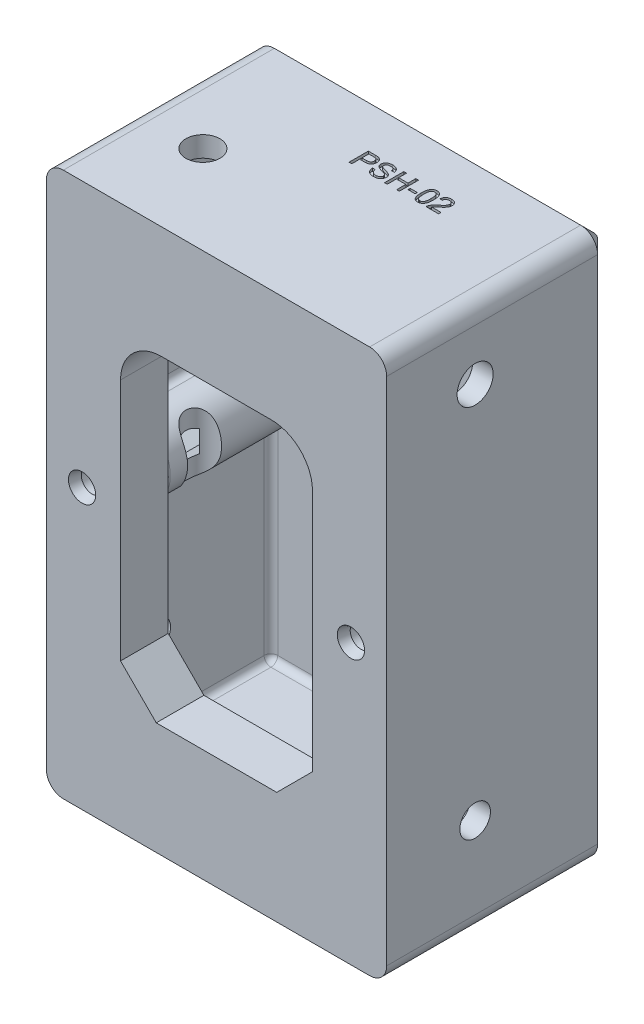
SolidWorks part; units mm, degrees
ref_plane "Front" through (0, 0, 0) normal (0, 0, 1) x (1, 0, 0)
ref_plane "Top" through (0, 0, 0) normal (0, 1, 0) x (1, 0, 0)
ref_plane "Right" through (0, 0, 0) normal (1, 0, 0) x (0, 0, -1)
sketch "Sketch3" plane through (0, 0, 0) normal (0, 0, 1) x (1, 0, 0)
  line L0 (10.9, 16.5) -> (0, 16.5) construction
  line L1 (0, 0) -> (50, 0)
  line L2 (0, 0) -> (0, 80)
  line L3 (0, 80) -> (50, 80)
  line L4 (50, 0) -> (50, 80)
  line L5 (10.9, 16.5) -> (39.1, 16.5)
  line L6 (10.9, 16.5) -> (10.9, 63.5)
  line L7 (10.9, 63.5) -> (39.1, 63.5)
  line L8 (39.1, 16.5) -> (39.1, 63.5)
  line L9 (39.1, 16.5) -> (50, 16.5) construction
  line L10 (10.9, 16.5) -> (10.9, 0) construction
  line L11 (10.9, 63.5) -> (10.9, 80) construction
  line L12 (25, 63.5) -> (25, 41) construction
  line L13 (25, 41) -> (25, 16.5) construction
  line L14 (25, 41) -> (5.25, 41) construction
  line L15 (25, 41) -> (44.75, 41) construction
  circle A0 centre (5.25, 41) radius 1.6 construction
  circle A1 centre (44.75, 41) radius 1.6 construction
  dimension "D5" = 39.5
  dimension "D6" = 3.2
  dimension "D1" = 50
  dimension "D2" = 80
  dimension "D3" = 28.2
  dimension "D4" = 22.5
  dimension "D7" = 24.5
extrude "Boss-Extrude1" add sketch "Sketch3" along normal blind 30
sketch "Sketch17" plane through (0, 0, 30) normal (0, 0, 1) x (1, 0, 0)
  circle A0 centre (44.75, 41) radius 1.6 construction
  circle A1 centre (5.25, 41) radius 1.6 construction
  circle A2 centre (44.75, 41) radius 1.6
  circle A3 centre (5.25, 41) radius 1.6
extrude "Cut-Extrude7" cut sketch "Sketch17" against normal through all
chamfer "Chamfer1" distance 0.4 angle 75 2 edges at (46.35, 41, 30) (6.85, 41, 30) first distance on face at (46.35, 41, 30)
sketch "Sketch4" plane through (0, 0, 0) normal (0, 0, -1) x (-1, 0, 0)
  line L4 (-47, 36.5349) -> (-47, 3)
  line L5 (-3, 45.4651) -> (-3, 77)
  line L8 (-47, 3) -> (-3, 3)
  line L9 (-3, 3) -> (-3, 77)
  line L10 (-47, 77) -> (-47, 3)
  line L11 (-3, 77) -> (-47, 77)
  line L12 (-47, 3) -> (-3, 3)
  line L13 (-3, 3) -> (-3, 36.5349)
  line L14 (-47, 77) -> (-47, 45.4651)
  line L15 (-3, 77) -> (-47, 77)
  arc A0 (-47, 36.5349) -> (-47, 45.4651) centre (-44.75, 41) ccw
  arc A1 (-3, 45.4651) -> (-3, 36.5349) centre (-5.25, 41) ccw
  dimension "D2" = 10
  dimension "D1" = 3
extrude "Cut-Extrude1" cut sketch "Sketch4" against normal offset from surface (23 mm away) 7 up to face at (42.75, 41, 30)
fillet "Fillet1" radius 2.5 4 edges at (0, 0, 15) (50, 0, 15) (50, 80, 15) (0, 80, 15)
fillet "Fillet2" radius 1 8 edges at (3, 3, 11.5) (47, 77, 11.5) (3, 36.5349, 11.5) (3, 45.4651, 11.5) (47, 36.5349, 11.5) (47, 45.4651, 11.5) (47, 3, 11.5) (3, 77, 11.5)
sketch "Sketch5" plane through (0, 0, 0) normal (-1, 0, 0) x (0, 0, 1)
  line L1 (0, 80) -> (30, 80) construction
  line L2 (17, 70) -> (17, 45) construction
  line L3 (17, 45) -> (17, 14.5) construction
  line L4 (30, 77.5) -> (30, 2.5) construction
  circle A0 centre (17, 70) radius 2.5
  circle A2 centre (17, 14.5) radius 2.25
  dimension "D1" = 13
  dimension "D2" = 5
  dimension "D3" = 10
  dimension "D4" = 25
  dimension "D5" = 14.5
  dimension "D6" = 4.5
extrude "Cut-Extrude2" cut sketch "Sketch5" against normal up to next
hole_wizard "M5 Clearance Hole1" positions "Sketch6" profile "Sketch7" hole size "M5" standard "ANSI Metric" end condition up to next
sketch "Sketch6" plane through (47, 0, 0) normal (-1, 0, 0) x (0, 0, 1)
  point P0 (17, 70)
sketch "Sketch7" plane through (47, 70, 17) normal (0, 1, 0) x (0, 0, 1)
  line L0 (0, 0) -> (0, 3)
  line L1 (0, 3) -> (2.65, 3)
  line L2 (2.65, 3) -> (2.65, 0)
  line L5 (2.65, 0) -> (0, 0)
  line L11 (0, -6.35) -> (0, 107.95) construction
  dimension "Thru Hole Dia." = 5.3
  dimension "Thru Hole Depth" = 3
sketch "Sketch8" plane through (0, 80, 0) normal (0, 1, 0) x (1, 0, 0)
  line L1 (0, -30) -> (0, 0) construction
  line L2 (47.5, -30) -> (2.5, -30) construction
  circle A0 centre (10, -17) radius 2.5
  dimension "D1" = 5
  dimension "D3" = 10
  dimension "D2" = 13
extrude "Cut-Extrude3" cut sketch "Sketch8" against normal up to surface (77 mm away) up to face at (25, 3, 11.5)
hole_wizard "M5 Clearance Hole2" positions "Sketch10" profile "Sketch11" hole size "M5" standard "ANSI Metric" end condition up to next
sketch "Sketch10" plane through (0, 3, 0) normal (0, 1, 0) x (1, 0, 0)
  point P0 (10, -17)
sketch "Sketch11" plane through (10, 3, 17) normal (1, 0, 0) x (0, 0, 1)
  line L0 (0, 0) -> (0, 3)
  line L1 (0, 3) -> (2.65, 3)
  line L2 (2.65, 3) -> (2.65, 0)
  line L5 (2.65, 0) -> (0, 0)
  line L11 (0, -6.35) -> (0, 107.95) construction
  dimension "Thru Hole Dia." = 5.3
  dimension "Thru Hole Depth" = 3
sketch "Sketch12" plane through (47, 0, 0) normal (-1, 0, 0) x (0, 0, 1)
  circle A0 centre (17, 14.5) radius 2.25 construction
  circle A1 centre (17, 14.5) radius 2.25
extrude "Cut-Extrude4" cut sketch "Sketch12" against normal through all
sketch "Sketch13" plane through (0, 80, 0) normal (0, 1, 0) x (1, 0, 0)
  line L0 (8, -8) -> (50, -8) construction
  line L1 (50, 0) -> (50, -30) construction
  line L2 (47.5, 0) -> (2.5, 0) construction
  text T0 "PSH-02"
  dimension "D1" = 8
extrude "Part Number" cut sketch "Sketch13" against normal blind 0.4
sketch "Sketch14" plane through (0, 0, 30) normal (0, 0, 1) x (1, 0, 0)
  line L1 (10.25, 68.5) -> (39.75, 68.5)
  line L2 (10.25, 68.5) -> (10.25, 11.5)
  line L3 (10.25, 11.5) -> (39.75, 11.5)
  line L4 (39.75, 68.5) -> (39.75, 11.5)
  line L6 (25, 68.5) -> (25, 63.5) construction
  line L7 (39.1, 63.5) -> (10.9, 63.5) construction
  line L8 (25, 11.5) -> (25, 16.5) construction
  line L9 (10.9, 16.5) -> (39.1, 16.5) construction
  dimension "D1" = 57
  dimension "D2" = 29.5
extrude "Omnicom Enlarged Socket Cavity" [suppressed] cut sketch "Sketch14" against normal through all
sketch "Sketch15" [suppressed] plane through (0, 0, 23) normal (0, 0, 1) x (1, 0, 0)
  line L0 (25, 40) -> (39.1, 40) construction
  line L1 (10, 9.5) -> (40, 9.5)
  line L2 (10, 9.5) -> (10, 70.5)
  line L3 (10, 70.5) -> (40, 70.5)
  line L4 (40, 9.5) -> (40, 70.5)
  line L5 (10, 9.5) -> (40, 70.5) construction
  line L6 (10, 70.5) -> (40, 9.5) construction
  line L7 (39.1, 16.4) -> (39.1, 63.6) construction
  line L8 (25, 40) -> (10.9, 40) construction
  line L9 (10.9, 63.6) -> (10.9, 16.4) construction
  point P0 (25, 40)
  dimension "D1" = 61
  dimension "D2" = 30
extrude "Astrodyne Enlarged Socket Cavity" [suppressed] cut sketch "Sketch15" against normal through all
sketch "Sketch16" [suppressed] plane through (0, 0, 23) normal (0, 0, 1) x (1, 0, 0)
  line L0 (25, 76) -> (25, 70.5) construction
  line L1 (40, 70.5) -> (10, 70.5) construction
  line L2 (25, 4) -> (25, 9.5) construction
  line L3 (10, 9.5) -> (40, 9.5) construction
  circle A0 centre (25, 76) radius 1.4
  circle A1 centre (25, 4) radius 1.4
  dimension "D1" = 72
  dimension "D2" = 2.8
extrude "Cut-Extrude6" [suppressed] cut sketch "Sketch16" against normal through all
chamfer "Chamfer2" [suppressed] distance 0.4 angle 70
ref_plane "Plane1" [suppressed] through (0, 0, 10) normal (0, 0, 1) x (1, 0, 0)
sketch "Sketch18" [suppressed] plane through (0, 0, 10) normal (0, 0, 1) x (1, 0, 0)
  line L0 (47, 70) -> (46.2, 70) construction
  line L1 (47, 72.65) -> (47, 67.35) construction
  line L2 (46.2, 70) -> (-6.9259, 84.235) construction
  line L3 (46.2, 70) -> (26.1844, 70) construction
  dimension "D1" = 15
  dimension "D2" = 55
  dimension "D3" = 0.8
ref_plane "Plane2" [suppressed] through (-6.9259, 84.235, 10) normal (-0.9659, 0.2588, 0) x (0, 0, 1)
sketch "Sketch19" [suppressed] plane through (-6.9259, 84.235, 10) normal (-0.9659, 0.2588, 0) x (0, 0, 1)
  line L0 (0, 0) -> (0, -5.1804) construction
  circle A0 centre (0, 0) radius 2
  dimension "D1" = 4
extrude "Cut-Extrude8" [suppressed] cut sketch "Sketch19" against normal up to surface (56.3641 mm away) up to face at (47, 70, 19.65)
chamfer "Chamfer3" distance 5.25 2 edges at (39.1, 16.5, 26.5) (10.9, 16.5, 26.5)
fillet "Fillet3" radius 6 2 edges at (39.1, 63.5, 26.5) (10.9, 63.5, 26.5)
sketch "Sketch22" plane through (0, 0, 0) normal (0, 0, -1) x (-1, 0, 0)
  line L0 (-33.5, 40) -> (-16.5, 40) construction
  line L1 (-33.5, 42.5) -> (-16.5, 42.5)
  line L2 (-33.5, 37.5) -> (-16.5, 37.5)
  line L3 (-25, 0) -> (-25, 80) construction
  line L4 (-47.5, 0) -> (-2.5, 0)
  line L5 (0, 2.5) -> (0, 77.5)
  line L6 (-2.5, 80) -> (-47.5, 80)
  line L7 (-50, 77.5) -> (-50, 2.5)
  line L8 (-47.5, 0) -> (-2.5, 0)
  line L9 (0, 2.5) -> (0, 77.5)
  line L10 (-2.5, 80) -> (-47.5, 80)
  line L11 (-50, 77.5) -> (-50, 2.5)
  arc A0 (-33.5, 42.5) -> (-33.5, 37.5) centre (-33.5, 40) ccw
  arc A1 (-16.5, 37.5) -> (-16.5, 42.5) centre (-16.5, 40) ccw
  arc A4 (-2.5, 0) -> (0, 2.5) centre (-2.5, 2.5) ccw
  arc A5 (0, 77.5) -> (-2.5, 80) centre (-2.5, 77.5) ccw
  arc A6 (-47.5, 80) -> (-50, 77.5) centre (-47.5, 77.5) ccw
  arc A7 (-50, 2.5) -> (-47.5, 0) centre (-47.5, 2.5) ccw
  arc A8 (-2.5, 0) -> (0, 2.5) centre (-2.5, 2.5) ccw
  arc A9 (0, 77.5) -> (-2.5, 80) centre (-2.5, 77.5) ccw
  arc A10 (-47.5, 80) -> (-50, 77.5) centre (-47.5, 77.5) ccw
  arc A11 (-50, 2.5) -> (-47.5, 0) centre (-47.5, 2.5) ccw
  point P12 (-25, 40)
  dimension "D2" = 5
  dimension "D3" = 17
  dimension "D4" = 40
  dimension "D1" = 0
extrude "Boss-Extrude2" add sketch "Sketch22" along normal blind 3
sketch "Sketch21" plane through (0, 0, 23) normal (0, 0, -1) x (-1, 0, 0)
  line L1 (-42, 39.4123) -> (-42, 42.5877)
  line L2 (-42, 42.5877) -> (-44.75, 44.1754)
  line L3 (-44.75, 44.1754) -> (-47.5, 42.5877)
  line L4 (-47.5, 42.5877) -> (-47.5, 39.4123)
  line L5 (-47.5, 39.4123) -> (-44.75, 37.8246)
  line L6 (-44.75, 37.8246) -> (-42, 39.4123)
  line L7 (-8, 39.4123) -> (-5.25, 37.8246)
  line L8 (-5.25, 37.8246) -> (-2.5, 39.4123)
  line L9 (-2.5, 39.4123) -> (-2.5, 42.5877)
  line L10 (-2.5, 42.5877) -> (-5.25, 44.1754)
  line L11 (-5.25, 44.1754) -> (-8, 42.5877)
  line L12 (-8, 42.5877) -> (-8, 39.4123)
  circle A0 centre (-44.75, 41) radius 2.75 construction
  circle A1 centre (-5.25, 41) radius 2.75 construction
  dimension "D1" = 5.5
extrude "Cut-Extrude9" cut sketch "Sketch21" against normal blind 2.5 and the other way through all
chamfer "Chamfer5" distance 2 angle 45 8 edges at (25, 0, -3) (0.7322, 0.7322, -3) (49.2678, 0.7322, -3) (0, 40, -3) (50, 40, -3) (0.7322, 79.2678, -3) (49.2678, 79.2678, -3) (25, 80, -3)
fillet "Fillet4" radius 1 32 edges at (3.2929, 76.7071, 23) (25, 77, 23) (46.7071, 76.7071, 23) (47, 61.4342, 23) (46.6292, 46.0911, 23) (39.75, 41, 23) (46.6292, 35.9089, 23) (47, 19.5658, 23) (46.7071, 3.2929, 23) (25, 3, 23) (3.2929, 3.2929, 23) (3, 19.5658, 23) (3.3708, 35.9089, 23) (10.25, 41, 23) (3.3708, 46.0911, 23) (3.2929, 76.7071, 0) (3, 61.4342, 0) (3.3708, 46.0911, 0) (10.25, 41, 0) (3.3708, 35.9089, 0) (3, 19.5658, 0) (3.2929, 3.2929, 0) (25, 3, 0) (46.7071, 3.2929, 0) (47, 19.5658, 0) (46.6292, 35.9089, 0) (39.75, 41, 0) (46.6292, 46.0911, 0) (47, 61.4342, 0) (46.7071, 76.7071, 0) (3, 61.4342, 23) (25, 77, 0)
